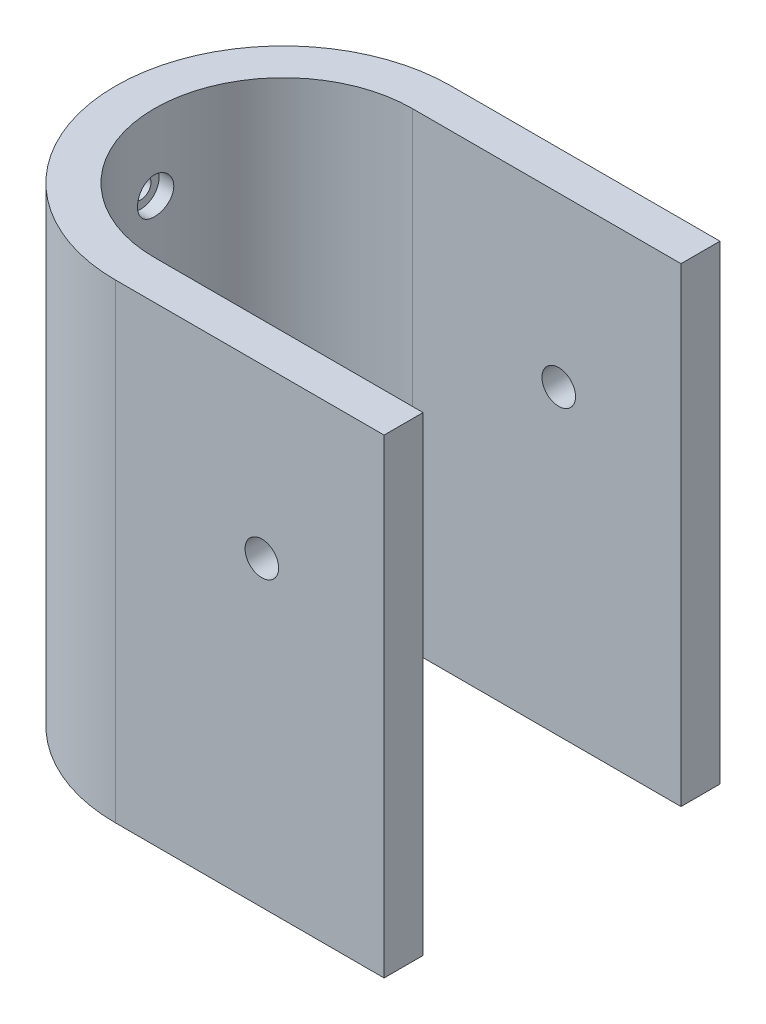
SolidWorks part; units mm, degrees
ref_plane "前视基准面" through (0, 0, 0) normal (0, 0, 1) x (1, 0, 0)
ref_plane "上视基准面" through (0, 0, 0) normal (0, 1, 0) x (1, 0, 0)
ref_plane "右视基准面" through (0, 0, 0) normal (1, 0, 0) x (0, 0, -1)
sketch "草图1" plane through (0, 0, 0) normal (0, 1, 0) x (1, 0, 0)
  line L0 (0, 25) -> (0, 19.2)
  line L1 (0, -19.2) -> (0, -25)
  line L2 (0, 25) -> (40, 25)
  line L3 (40, 25) -> (40, 19.2)
  line L4 (40, 19.2) -> (0, 19.2)
  arc A0 (0, 19.2) -> (0, -19.2) centre (0, 0) ccw
  arc A1 (0, 25) -> (0, -25) centre (0, 0) ccw
  dimension "D1" = 38.4
  dimension "D2" = 50
  dimension "D3" = 40
extrude "凸台-拉伸1" add sketch "草图1" along normal blind 70 contours L0 A1 A0 region at (-0.559, 0, -22.1)
sketch "草图2" plane through (0, 0, 0) normal (1, 0, 0) x (0, 0, -1)
  circle A0 centre (0, 58.75) radius 1.5
  circle A1 centre (0, 44.75) radius 1.5
  circle A2 centre (0, 24) radius 1.5
  circle A3 centre (0, 10) radius 1.5
  circle A4 centre (0, 58.75) radius 2.6
  circle A5 centre (0, 44.75) radius 2.6
  circle A6 centre (0, 24) radius 2.6
  circle A7 centre (0, 10) radius 2.6
  dimension "D4" = 3
  dimension "D5" = 3
  dimension "D6" = 3
  dimension "D7" = 3
  dimension "D9" = 5.2
  dimension "D10" = 5.2
  dimension "D11" = 5.2
  dimension "D12" = 5.2
  dimension "D1" = 14
  dimension "D2" = 14
  dimension "D3" = 20.75
  dimension "D8" = 10
extrude "切除-拉伸1" cut sketch "草图2" against normal through all and the other way blind 3 contours A0 | A1 | A2 | A3
sketch "草图6" plane through (0, 0, 0) normal (1, 0, 0) x (0, 0, -1)
  circle A0 centre (0, 10) radius 1.5 construction
  circle A1 centre (0, 24) radius 1.5 construction
  circle A2 centre (0, 44.75) radius 1.5 construction
  circle A3 centre (0, 58.75) radius 1.5 construction
  circle A4 centre (0, 10) radius 1.5
  circle A5 centre (0, 24) radius 1.5
  circle A6 centre (0, 44.75) radius 1.5
  circle A7 centre (0, 58.75) radius 1.5
  circle A8 centre (0, 58.75) radius 2.7
  circle A9 centre (0, 44.75) radius 2.7
  circle A10 centre (0, 24) radius 2.7
  circle A11 centre (0, 10) radius 2.7
  dimension "D1" = 5.4
  dimension "D2" = 5.4
  dimension "D3" = 5.4
  dimension "D4" = 5.4
extrude "切除-拉伸3" cut sketch "草图6" against normal blind 21.2
sketch "草图7" plane through (0, 70, 0) normal (0, 1, 0) x (1, 0, 0)
  line L0 (0, 25) -> (40, 25)
  line L1 (40, 25) -> (40, 19.2)
  line L2 (0, 19.2) -> (0, 25)
  line L3 (0, -25) -> (0, -19.2)
  line L4 (0, 19.2) -> (0, 25)
  line L5 (0, -25) -> (0, -19.2)
  line L6 (40, 19.2) -> (0, 19.2)
  line L7 (-13.75, 0) -> (13.75, 0) construction
  line L8 (40, -19.2) -> (0, -19.2)
  line L9 (40, -25) -> (40, -19.2)
  line L10 (0, -25) -> (40, -25)
  arc A2 (0, 25) -> (0, -25) centre (0, 0) ccw
  arc A3 (0, 19.2) -> (0, -19.2) centre (0, 0) ccw
  arc A4 (0, 25) -> (0, -25) centre (0, 0) ccw
  arc A5 (0, 19.2) -> (0, -19.2) centre (0, 0) ccw
  line M8 (0, 19.2) -> (0, 25)
  line M10 (0, -25) -> (0, -19.2)
  dimension "D2" = 40
  dimension "D1" = 0
extrude "凸台-拉伸2" add sketch "草图7" against normal up to surface (70 mm away) contours L6 L1 L0 M8 | L10 L9 L8 M10 region at (20, 70, -22.1) region at (20, 70, 22.1) up to face at (-11.05, 0, 0)
sketch "草图8" plane through (0, 0, 25) normal (0, 0, 1) x (1, 0, 0)
  line L4 (0, 0) -> (40, 0)
  line L5 (40, 0) -> (40, 70)
  line L6 (40, 70) -> (0, 70)
  line L7 (0, 70) -> (0, 0)
  line L8 (0, 0) -> (40, 0)
  line L9 (40, 0) -> (40, 70)
  line L10 (40, 70) -> (0, 70)
  line L11 (0, 70) -> (0, 0)
  circle A0 centre (21.8, 45) radius 2.5
  point P2 (21.8, 45)
  dimension "D4" = 5
  dimension "D2" = 21.8
  dimension "D3" = 25
  dimension "D1" = 0
extrude "切除-拉伸4" cut sketch "草图8" against normal up to surface (50 mm away) contours A0 region at (21.8, 45, 25) up to face at (20, 35, -25)
